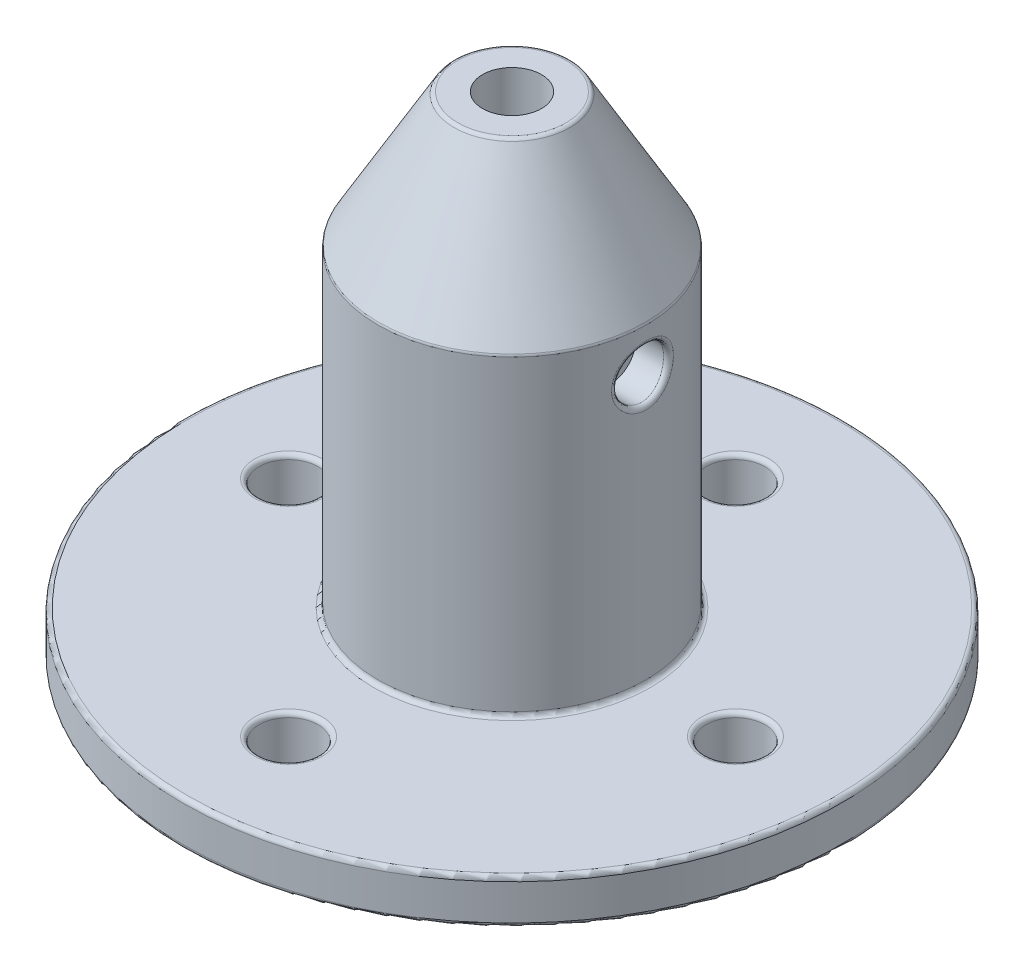
SolidWorks part; units mm, degrees
material "ABS"
ref_plane "Front Plane" through (0, 0, 0) normal (0, 0, 1) x (1, 0, 0)
ref_plane "Top Plane" through (0, 0, 0) normal (0, 1, 0) x (1, 0, 0)
ref_plane "Right Plane" through (0, 0, 0) normal (1, 0, 0) x (0, 0, -1)
sketch "Sketch1" plane through (0, 0, 0) normal (0, 1, 0) x (1, 0, 0)
  circle A0 centre (0, 0) radius 36.875
  dimension "D1" = 73.75
extrude "Boss-Extrude1" add sketch "Sketch1" along normal blind 5
sketch "Sketch2" plane through (0, 5, 0) normal (0, 1, 0) x (1, 0, 0)
  circle A0 centre (0, 0) radius 15
  circle A1 centre (0, 0) radius 3.3
  dimension "D1" = 30
  dimension "D2" = 6.6
extrude "Boss-Extrude2" add sketch "Sketch2" along normal blind 50
hole_wizard "M6 Clearance Hole1" positions "Sketch4" profile "Sketch3" hole size "M6" standard "ANSI Metric" end condition through all
sketch "Sketch4" plane through (0, 5, 0) normal (0, 1, 0) x (1, 0, 0)
  point P0 (0, -25)
  point P6 (-25, 0)
  point P7 (0, 25)
  point P8 (25, 0)
  dimension "D2" = 25
  dimension "D1" = 4
sketch "Sketch3" plane through (0, 5, 25) normal (1, 0, 0) x (0, 0, 1)
  line L0 (0, 0) -> (0, 5)
  line L1 (0, 5) -> (3.3, 5)
  line L2 (3.3, 5) -> (3.3, 0)
  line L5 (3.3, 0) -> (0, 0)
  line L11 (0, -6.35) -> (0, 107.95) construction
  dimension "Thru Hole Dia." = 6.6
  dimension "Thru Hole Depth" = 5
chamfer "Chamfer1" distance 15 angle 30 1 edges at (0, 55, 15) first distance on face at (0, 55, 15)
ref_plane "Plane1" through (6, 0, 0) normal (1, 0, 0) x (0, 0, -1)
ref_axis "Axis1" through (0, 57.75, 0) along (0, -1, 0)
ref_plane "Plane2" through (0, 0, 0) normal (-0.866, 0, 0.5) x (0, -1, 0)
ref_plane "Plane3" through (-5.1962, 0, 3) normal (-0.866, 0, 0.5) x (0, -1, 0)
sketch "Sketch8" plane through (6, 0, 0) normal (1, 0, 0) x (0, 0, -1)
  line L0 (0, 57.75) -> (0, -2.75) construction
  circle A0 centre (0, 35) radius 1.6
  dimension "D1" = 3.2
  dimension "D2" = 35
extrude "Cut-Extrude3" cut sketch "Sketch8" against normal blind 6 and the other way through all
sketch "Sketch9" plane through (-5.1962, 0, 3) normal (-0.866, 0, 0.5) x (0, -1, 0)
  line L0 (-57.75, 0) -> (2.75, 0) construction
  circle A0 centre (-35, 0) radius 1.6
  dimension "D2" = 3.2
  dimension "D1" = 35
extrude "Cut-Extrude4" cut sketch "Sketch9" against normal blind 6 and the other way through all
sketch "Sketch5" plane through (6, 0, 0) normal (1, 0, 0) x (0, 0, -1)
  line L0 (0, 57.75) -> (0, -2.75) construction
  line L1 (0, 38.4179) -> (-2.96, 36.709)
  line L2 (-2.96, 36.709) -> (-2.96, 33.291)
  line L3 (-2.96, 33.291) -> (0, 31.5821)
  line L4 (0, 31.5821) -> (2.96, 33.291)
  line L5 (2.96, 33.291) -> (2.96, 36.709)
  line L6 (2.96, 36.709) -> (0, 38.4179)
  circle A0 centre (0, 35) radius 2.96 construction
  circle A1 centre (0, 35) radius 1.6 construction
  dimension "D1" = 5.92
extrude "Cut-Extrude1" cut sketch "Sketch5" against normal mid plane 2.76
sketch "Sketch6" plane through (-5.1962, 0, 3) normal (-0.866, 0, 0.5) x (0, -1, 0)
  line L0 (-57.75, 0) -> (2.75, 0) construction
  line L1 (-31.5821, 0) -> (-33.291, 2.96)
  line L2 (-33.291, 2.96) -> (-36.709, 2.96)
  line L3 (-36.709, 2.96) -> (-38.4179, 0)
  line L4 (-38.4179, 0) -> (-36.709, -2.96)
  line L5 (-36.709, -2.96) -> (-33.291, -2.96)
  line L6 (-33.291, -2.96) -> (-31.5821, 0)
  circle A0 centre (-35, 0) radius 2.96 construction
  circle A1 centre (-35, 0) radius 1.6 construction
  dimension "D1" = 5.92
extrude "Cut-Extrude2" cut sketch "Sketch6" against normal mid plane 2.76
ref_plane "Plane4" through (11, 0, 0) normal (1, 0, 0) x (0, 0, -1)
ref_plane "Plane5" through (-9.5263, 0, 5.5) normal (-0.866, 0, 0.5) x (0, -1, 0)
sketch "Sketch11" plane through (11, 0, 0) normal (1, 0, 0) x (0, 0, -1)
  line L0 (0, 57.75) -> (0, -2.75) construction
  circle A0 centre (0, 35) radius 2.85
  circle A1 centre (0, 35) radius 1.6 construction
  dimension "D1" = 5.7
extrude "Cut-Extrude5" cut sketch "Sketch11" along normal through all
sketch "Sketch13" plane through (-9.5263, 0, 5.5) normal (-0.866, 0, 0.5) x (0, -1, 0)
  circle A0 centre (-35, 0) radius 2.85
  dimension "D1" = 5.7
extrude "Cut-Extrude6" cut sketch "Sketch13" along normal through all
fillet "Fillet1" radius 0.5 11 edges at (-25, 5, 3.3) (0, 5, 28.3) (25, 5, 3.3) (0, 5, -21.7) (0, 0, 36.875) (0, 5, 36.875) (0, 5, 15) (0, 40, 15) (0, 55, 6.3397) (-11.3711, 35.5985, 9.7826) (14.7389, 35.5985, -2.7865)
